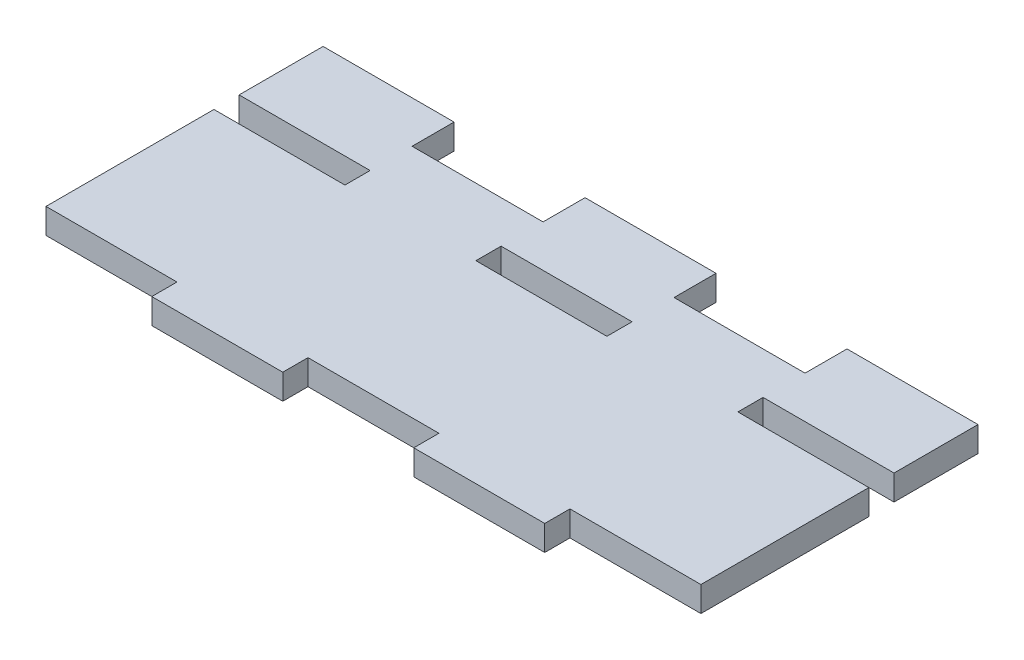
SolidWorks part; units mm, degrees
ref_plane "Front Plane" through (0, 0, 0) normal (0, 0, 1) x (1, 0, 0)
ref_plane "Top Plane" through (0, 0, 0) normal (0, 1, 0) x (1, 0, 0)
ref_plane "Right Plane" through (0, 0, 0) normal (1, 0, 0) x (0, 0, -1)
sketch "Sketch1" plane through (0, 0, 0) normal (0, 1, 0) x (1, 0, 0)
  line L0 (-23.4, 13) -> (-7.8, 13)
  line L1 (-39, 18) -> (-23.4, 18)
  line L2 (-39, 18) -> (-39, 8)
  line L4 (39, 18) -> (39, 8)
  line L6 (-7.8, 18) -> (7.8, 18)
  line L8 (23.4, 18) -> (39, 18)
  line L9 (-23.4, 18) -> (-23.4, 13)
  line L10 (-7.8, 18) -> (-7.8, 13)
  line L11 (7.8, 18) -> (7.8, 13)
  line L12 (23.4, 18) -> (23.4, 13)
  line L13 (7.8, 13) -> (23.4, 13)
  line L14 (-39, 8) -> (-23.4, 8)
  line L15 (-39, 5) -> (-23.4, 5)
  line L16 (-39, -15) -> (-23.4, -15)
  line L17 (-7.8, 8) -> (7.8, 8)
  line L18 (-7.8, 5) -> (7.8, 5)
  line L19 (23.4, 8) -> (39, 8)
  line L20 (-23.4, 8) -> (-23.4, 5)
  line L21 (-7.8, 8) -> (-7.8, 5)
  line L22 (7.8, 8) -> (7.8, 5)
  line L23 (23.4, 8) -> (23.4, 5)
  line L24 (-39, 5) -> (-39, -15)
  line L25 (39, 5) -> (39, -15)
  line L26 (23.4, 5) -> (39, 5)
  line L27 (-23.4, -18) -> (-7.8, -18)
  line L29 (7.8, -18) -> (23.4, -18)
  line L31 (-23.4, -18) -> (-23.4, -15)
  line L32 (-7.8, -18) -> (-7.8, -15)
  line L33 (7.8, -18) -> (7.8, -15)
  line L34 (23.4, -18) -> (23.4, -15)
  line L35 (-7.8, -15) -> (7.8, -15)
  line L36 (23.4, -15) -> (39, -15)
  point P0 (0, 0)
  dimension "D1" = 78
  dimension "D3" = 5
  dimension "D4" = 5
  dimension "D5" = 3
  dimension "D6" = 20
extrude "Boss-Extrude1" add sketch "Sketch1" along normal blind 3
